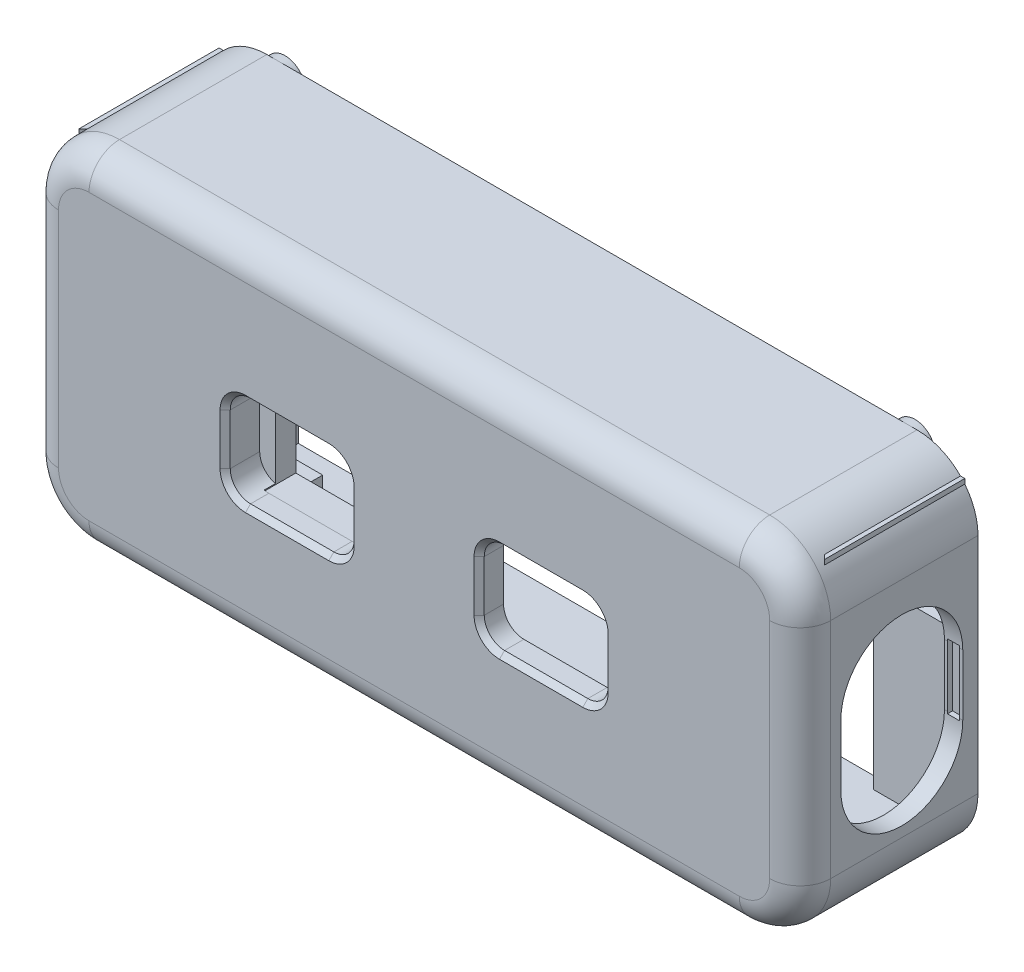
SolidWorks part; units mm, degrees
ref_plane "Front Plane" through (0, 0, 0) normal (0, 0, 1) x (1, 0, 0)
ref_plane "Top Plane" through (0, 0, 0) normal (0, 1, 0) x (1, 0, 0)
ref_plane "Right Plane" through (0, 0, 0) normal (1, 0, 0) x (0, 0, -1)
sketch "Sketch1" plane through (0, 0, 0) normal (0, 0, 1) x (1, 0, 0)
  line L0 (-32, 40) -> (32, 40)
  line L1 (38, 46) -> (38, 68)
  line L2 (32, 74) -> (-32, 74)
  line L3 (-38, 68) -> (-38, 46)
  arc A0 (-38, 46) -> (-32, 40) centre (-32, 46) ccw
  arc A1 (32, 40) -> (38, 46) centre (32, 46) ccw
  arc A2 (38, 68) -> (32, 74) centre (32, 68) ccw
  arc A3 (-32, 74) -> (-38, 68) centre (-32, 68) ccw
extrude "Boss-Extrude1" add sketch "Sketch1" along normal blind 17.5 from offset 80.8
fillet "Fillet1" radius 3 8 edges at (36.2426, 72.2426, 98.3) (38, 57, 98.3) (36.2426, 41.7574, 98.3) (0, 40, 98.3) (-36.2426, 41.7574, 98.3) (-38, 57, 98.3) (-36.2426, 72.2426, 98.3) (0, 74, 98.3)
sketch "Sketch2" plane through (0, 0, 0) normal (0, 0, 1) x (1, 0, 0)
  line L0 (-32.6, 42.4) -> (32.6, 42.4)
  line L1 (36.2, 46) -> (36.2, 68)
  line L2 (32, 72.2) -> (-32, 72.2)
  line L3 (-36.2, 68) -> (-36.2, 46)
  arc A0 (-36.2, 46) -> (-32.6, 42.4) centre (-32.6, 46) ccw
  arc A1 (32.6, 42.4) -> (36.2, 46) centre (32.6, 46) ccw
  arc A2 (36.2, 68) -> (32, 72.2) centre (32, 68) ccw
  arc A3 (-32, 72.2) -> (-36.2, 68) centre (-32, 68) ccw
extrude "Boss-Extrude2" add sketch "Sketch2" along normal blind 16.1 from offset 79.8 separate body
combine bodies "Combine1" operation type subtract main body 101 bodies to subtract 102
sketch "Sketch3" plane through (0, 0, 0) normal (0, 0, 1) x (1, 0, 0)
  line L1 (-36.7, 65.3) -> (-28.9, 65.3)
  line L2 (-36.7, 65.3) -> (-36.7, 72.21)
  line L3 (-36.7, 72.21) -> (-28.9, 72.21)
  line L4 (-28.9, 65.3) -> (-28.9, 72.21)
extrude "Boss-Extrude3" add sketch "Sketch3" along normal blind 6 from offset 80.8
sketch "Sketch4" plane through (0, 0, 0) normal (0, 1, 0) x (1, 0, 0)
  line L0 (-28.9, -86.8) -> (-36.7, -86.8)
  line L1 (-36.7, -86.8) -> (-36.7, -94.6)
  line L2 (-36.7, -94.6) -> (-28.9, -86.8)
extrude "Boss-Extrude4" add sketch "Sketch4" along normal blind 6.91 from offset 65.3
sketch "Sketch5" plane through (0, 0, 0) normal (0, 0, 1) x (1, 0, 0)
  line L1 (-36.21, 42.39) -> (-28.9, 42.39)
  line L2 (-36.21, 42.39) -> (-36.21, 60)
  line L3 (-36.21, 60) -> (-28.9, 60)
  line L4 (-28.9, 42.39) -> (-28.9, 60)
extrude "Boss-Extrude5" add sketch "Sketch5" along normal blind 1.2 from offset 80.8
sketch "Sketch6" plane through (0, 0, 0) normal (0, 0, 1) x (1, 0, 0)
  line L1 (-26, 42.39) -> (-22, 42.39)
  line L2 (-26, 42.39) -> (-26, 45.4)
  line L3 (-26, 45.4) -> (-22, 45.4)
  line L4 (-22, 42.39) -> (-22, 45.4)
extrude "Boss-Extrude6" add sketch "Sketch6" along normal blind 2 from offset 85.3
sketch "Sketch7" plane through (0, 0, 0) normal (0, 0, 1) x (1, 0, 0)
  line L1 (-26, 69.2) -> (-22, 69.2)
  line L2 (-26, 69.2) -> (-26, 72.21)
  line L3 (-26, 72.21) -> (-22, 72.21)
  line L4 (-22, 69.2) -> (-22, 72.21)
extrude "Boss-Extrude7" add sketch "Sketch7" along normal blind 2 from offset 85.3
sketch "Sketch8" plane through (0, 0, 0) normal (1, 0, 0) x (0, 0, -1)
  line L0 (-94.3, 53) -> (-94.3, 59)
  line L1 (-82.3, 59) -> (-82.3, 53)
  arc A0 (-82.3, 53) -> (-88.3, 47) centre (-88.3, 53) cw
  arc A1 (-88.3, 47) -> (-94.3, 53) centre (-88.3, 53) cw
  arc A2 (-94.3, 59) -> (-88.3, 65) centre (-88.3, 59) cw
  arc A3 (-88.3, 65) -> (-82.3, 59) centre (-88.3, 59) cw
extrude "Boss-Extrude8" add sketch "Sketch8" along normal blind 3.3 from offset 39 separate body offset against normal yes
combine bodies "Combine2" operation type subtract main body 108 bodies to subtract 109
sketch "Sketch9" plane through (0, 0, 0) normal (0, 0, 1) x (1, 0, 0)
  line L1 (-37.7, 52.8) -> (-36.5, 52.8)
  line L2 (-37.7, 52.8) -> (-37.7, 59.2)
  line L3 (-37.7, 59.2) -> (-36.5, 59.2)
  line L4 (-36.5, 52.8) -> (-36.5, 59.2)
extrude "Boss-Extrude9" add sketch "Sketch9" along normal blind 0.6 from offset 81.8 separate body
combine bodies "Combine3" operation type subtract main body 110 bodies to subtract 111
sketch "Sketch10" plane through (0, 0, 0) normal (0, 0, 1) x (1, 0, 0)
  line L1 (-37.7, 52.8) -> (-36.5, 52.8)
  line L2 (-37.7, 52.8) -> (-37.7, 59.2)
  line L3 (-37.7, 59.2) -> (-36.5, 59.2)
  line L4 (-36.5, 52.8) -> (-36.5, 59.2)
extrude "Boss-Extrude10" add sketch "Sketch10" along normal blind 0.6 from offset 94.2 separate body
combine bodies "Combine4" operation type subtract main body 112 bodies to subtract 113
sketch "Sketch11" plane through (0, 0, 0) normal (0, 0, 1) x (1, 0, 0)
  line L1 (28.9, 65.3) -> (36.7, 65.3)
  line L2 (28.9, 65.3) -> (28.9, 72.21)
  line L3 (28.9, 72.21) -> (36.7, 72.21)
  line L4 (36.7, 65.3) -> (36.7, 72.21)
extrude "Boss-Extrude11" add sketch "Sketch11" along normal blind 6 from offset 80.8
sketch "Sketch12" plane through (0, 0, 0) normal (0, 1, 0) x (1, 0, 0)
  line L0 (28.9, -86.8) -> (36.7, -86.8)
  line L1 (36.7, -86.8) -> (36.7, -94.6)
  line L2 (36.7, -94.6) -> (28.9, -86.8)
extrude "Boss-Extrude12" add sketch "Sketch12" along normal blind 6.91 from offset 65.3
sketch "Sketch13" plane through (0, 0, 0) normal (0, 0, 1) x (1, 0, 0)
  line L1 (28.9, 42.39) -> (36.21, 42.39)
  line L2 (28.9, 42.39) -> (28.9, 60)
  line L3 (28.9, 60) -> (36.21, 60)
  line L4 (36.21, 42.39) -> (36.21, 60)
extrude "Boss-Extrude13" add sketch "Sketch13" along normal blind 1.2 from offset 80.8
sketch "Sketch14" plane through (0, 0, 0) normal (0, 0, 1) x (1, 0, 0)
  line L1 (22, 42.39) -> (26, 42.39)
  line L2 (22, 42.39) -> (22, 45.4)
  line L3 (22, 45.4) -> (26, 45.4)
  line L4 (26, 42.39) -> (26, 45.4)
extrude "Boss-Extrude14" add sketch "Sketch14" along normal blind 2 from offset 85.3
sketch "Sketch15" plane through (0, 0, 0) normal (0, 0, 1) x (1, 0, 0)
  line L1 (22, 69.2) -> (26, 69.2)
  line L2 (22, 69.2) -> (22, 72.21)
  line L3 (22, 72.21) -> (26, 72.21)
  line L4 (26, 69.2) -> (26, 72.21)
extrude "Boss-Extrude15" add sketch "Sketch15" along normal blind 2 from offset 85.3
sketch "Sketch16" plane through (0, 0, 0) normal (1, 0, 0) x (0, 0, -1)
  line L0 (-94.3, 53) -> (-94.3, 59)
  line L1 (-82.3, 59) -> (-82.3, 53)
  arc A0 (-82.3, 53) -> (-88.3, 47) centre (-88.3, 53) cw
  arc A1 (-88.3, 47) -> (-94.3, 53) centre (-88.3, 53) cw
  arc A2 (-94.3, 59) -> (-88.3, 65) centre (-88.3, 59) cw
  arc A3 (-88.3, 65) -> (-82.3, 59) centre (-88.3, 59) cw
extrude "Boss-Extrude16" add sketch "Sketch16" along normal blind 3.3 from offset 35.7 separate body
combine bodies "Combine5" operation type subtract main body 119 bodies to subtract 120
sketch "Sketch17" plane through (0, 0, 0) normal (0, 0, 1) x (1, 0, 0)
  line L1 (36.5, 52.8) -> (37.7, 52.8)
  line L2 (36.5, 52.8) -> (36.5, 59.2)
  line L3 (36.5, 59.2) -> (37.7, 59.2)
  line L4 (37.7, 52.8) -> (37.7, 59.2)
extrude "Boss-Extrude17" add sketch "Sketch17" along normal blind 0.6 from offset 81.8 separate body
combine bodies "Combine6" operation type subtract main body 121 bodies to subtract 122
sketch "Sketch18" plane through (0, 0, 0) normal (0, 0, 1) x (1, 0, 0)
  line L1 (36.5, 52.8) -> (37.7, 52.8)
  line L2 (36.5, 52.8) -> (36.5, 59.2)
  line L3 (36.5, 59.2) -> (37.7, 59.2)
  line L4 (37.7, 52.8) -> (37.7, 59.2)
extrude "Boss-Extrude18" add sketch "Sketch18" along normal blind 0.6 from offset 94.2 separate body
combine bodies "Combine7" operation type subtract main body 123 bodies to subtract 124
sketch "Sketch19" plane through (0, 0, 0) normal (0, 0, 1) x (1, 0, 0)
  circle A0 centre (-31, 68.3) radius 2
extrude "Boss-Extrude19" add sketch "Sketch19" along normal blind 0.81 from offset 80
sketch "Sketch20" plane through (0, 0, 0) normal (0, 0, 1) x (1, 0, 0)
  circle A0 centre (-31, 68.3) radius 1
extrude "Boss-Extrude20" add sketch "Sketch20" along normal blind 8 from offset 79.8 separate body
combine bodies "Combine8" operation type subtract main body 126 bodies to subtract 127
sketch "Sketch21" plane through (0, 0, 0) normal (0, 0, 1) x (1, 0, 0)
  circle A0 centre (-31, 72) radius 2
extrude "Boss-Extrude21" add sketch "Sketch21" along normal blind 0.81 from offset 80
sketch "Sketch22" plane through (0, 0, 0) normal (0, 0, 1) x (1, 0, 0)
  circle A0 centre (-31, 72) radius 1
extrude "Boss-Extrude22" add sketch "Sketch22" along normal blind 8 from offset 79.8 separate body
combine bodies "Combine9" operation type subtract main body 129 bodies to subtract 130
sketch "Sketch23" plane through (0, 0, 0) normal (0, 0, 1) x (1, 0, 0)
  circle A0 centre (31, 68.3) radius 2
extrude "Boss-Extrude23" add sketch "Sketch23" along normal blind 0.81 from offset 80
sketch "Sketch24" plane through (0, 0, 0) normal (0, 0, 1) x (1, 0, 0)
  circle A0 centre (31, 68.3) radius 1
extrude "Boss-Extrude24" add sketch "Sketch24" along normal blind 8 from offset 79.8 separate body
combine bodies "Combine10" operation type subtract main body 132 bodies to subtract 133
sketch "Sketch25" plane through (0, 0, 0) normal (0, 0, 1) x (1, 0, 0)
  circle A0 centre (31, 72) radius 2
extrude "Boss-Extrude25" add sketch "Sketch25" along normal blind 0.81 from offset 80
sketch "Sketch26" plane through (0, 0, 0) normal (0, 0, 1) x (1, 0, 0)
  circle A0 centre (31, 72) radius 1
extrude "Boss-Extrude26" add sketch "Sketch26" along normal blind 8 from offset 79.8 separate body
combine bodies "Combine11" operation type subtract main body 135 bodies to subtract 136
sketch "Sketch27" plane through (0, 0, 0) normal (0, 0, 1) x (1, 0, 0)
  line L1 (-19, 49.9) -> (-6, 49.9)
  line L2 (-19, 49.9) -> (-19, 62.9)
  line L3 (-19, 62.9) -> (-6, 62.9)
  line L4 (-6, 49.9) -> (-6, 62.9)
extrude "Boss-Extrude27" add sketch "Sketch27" along normal blind 3.01 from offset 92.9
sketch "Sketch28" plane through (0, 0, 0) normal (0, 0, 1) x (1, 0, 0)
  line L1 (-17.05, 51.85) -> (-7.95, 51.85)
  line L2 (-17.05, 51.85) -> (-17.05, 60.95)
  line L3 (-17.05, 60.95) -> (-7.95, 60.95)
  line L4 (-7.95, 51.85) -> (-7.95, 60.95)
extrude "Boss-Extrude28" add sketch "Sketch28" along normal blind 4.1 from offset 91.9 separate body
combine bodies "Combine12" operation type subtract main body 138 bodies to subtract 139
sketch "Sketch29" plane through (0, 0, 0) normal (0, 0, 1) x (1, 0, 0)
  line L1 (2.2, 42.39) -> (22.8, 42.39)
  line L2 (2.2, 42.39) -> (2.2, 48.6)
  line L3 (2.2, 48.6) -> (22.8, 48.6)
  line L4 (22.8, 42.39) -> (22.8, 48.6)
extrude "Boss-Extrude29" add sketch "Sketch29" along normal blind 2.51 from offset 93.4
sketch "Sketch30" plane through (0, 0, 0) normal (0, 0, 1) x (1, 0, 0)
  line L1 (1, 42.39) -> (2.2, 42.39)
  line L2 (1, 42.39) -> (1, 72.21)
  line L3 (1, 72.21) -> (2.2, 72.21)
  line L4 (2.2, 42.39) -> (2.2, 72.21)
extrude "Boss-Extrude30" add sketch "Sketch30" along normal blind 2.51 from offset 93.4
sketch "Sketch31" plane through (0, 0, 0) normal (0, 0, 1) x (1, 0, 0)
  line L1 (22.8, 42.39) -> (24, 42.39)
  line L2 (22.8, 42.39) -> (22.8, 72.21)
  line L3 (22.8, 72.21) -> (24, 72.21)
  line L4 (24, 42.39) -> (24, 72.21)
extrude "Boss-Extrude31" add sketch "Sketch31" along normal blind 2.51 from offset 93.4
sketch "Sketch32" plane through (0, 0, 0) normal (0, 0, 1) x (1, 0, 0)
  line L0 (-16.6, 51.9) -> (-8.4, 51.9)
  line L1 (-6.4, 53.9) -> (-6.4, 58.9)
  line L2 (-8.4, 60.9) -> (-16.6, 60.9)
  line L3 (-18.6, 58.9) -> (-18.6, 53.9)
  arc A0 (-18.6, 53.9) -> (-16.6, 51.9) centre (-16.6, 53.9) ccw
  arc A1 (-8.4, 51.9) -> (-6.4, 53.9) centre (-8.4, 53.9) ccw
  arc A2 (-6.4, 58.9) -> (-8.4, 60.9) centre (-8.4, 58.9) ccw
  arc A3 (-16.6, 60.9) -> (-18.6, 58.9) centre (-16.6, 58.9) ccw
extrude "Boss-Extrude32" add sketch "Sketch32" along normal blind 4.4 from offset 94.9 separate body
combine bodies "Combine13" operation type subtract main body 143 bodies to subtract 144
chamfer "Chamfer1" distance 0.5 angle 45 8 edges at (-12.5, 51.9, 98.3) (-18.0142, 52.4858, 98.3) (-6.9858, 52.4858, 98.3) (-18.6, 56.4, 98.3) (-6.4, 56.4, 98.3) (-18.0142, 60.3142, 98.3) (-6.9858, 60.3142, 98.3) (-12.5, 60.9, 98.3)
sketch "Sketch33" plane through (0, 0, 0) normal (0, 0, 1) x (1, 0, 0)
  line L0 (8.4, 51.9) -> (16.6, 51.9)
  line L1 (18.6, 53.9) -> (18.6, 58.9)
  line L2 (16.6, 60.9) -> (8.4, 60.9)
  line L3 (6.4, 58.9) -> (6.4, 53.9)
  arc A0 (6.4, 53.9) -> (8.4, 51.9) centre (8.4, 53.9) ccw
  arc A1 (16.6, 51.9) -> (18.6, 53.9) centre (16.6, 53.9) ccw
  arc A2 (18.6, 58.9) -> (16.6, 60.9) centre (16.6, 58.9) ccw
  arc A3 (8.4, 60.9) -> (6.4, 58.9) centre (8.4, 58.9) ccw
extrude "Boss-Extrude33" add sketch "Sketch33" along normal blind 4.4 from offset 94.9 separate body
combine bodies "Combine14" operation type subtract main body 145 bodies to subtract 146
chamfer "Chamfer2" distance 0.5 angle 45 8 edges at (12.5, 51.9, 98.3) (6.9858, 52.4858, 98.3) (18.0142, 52.4858, 98.3) (6.4, 56.4, 98.3) (18.6, 56.4, 98.3) (6.9858, 60.3142, 98.3) (18.0142, 60.3142, 98.3) (12.5, 60.9, 98.3)
